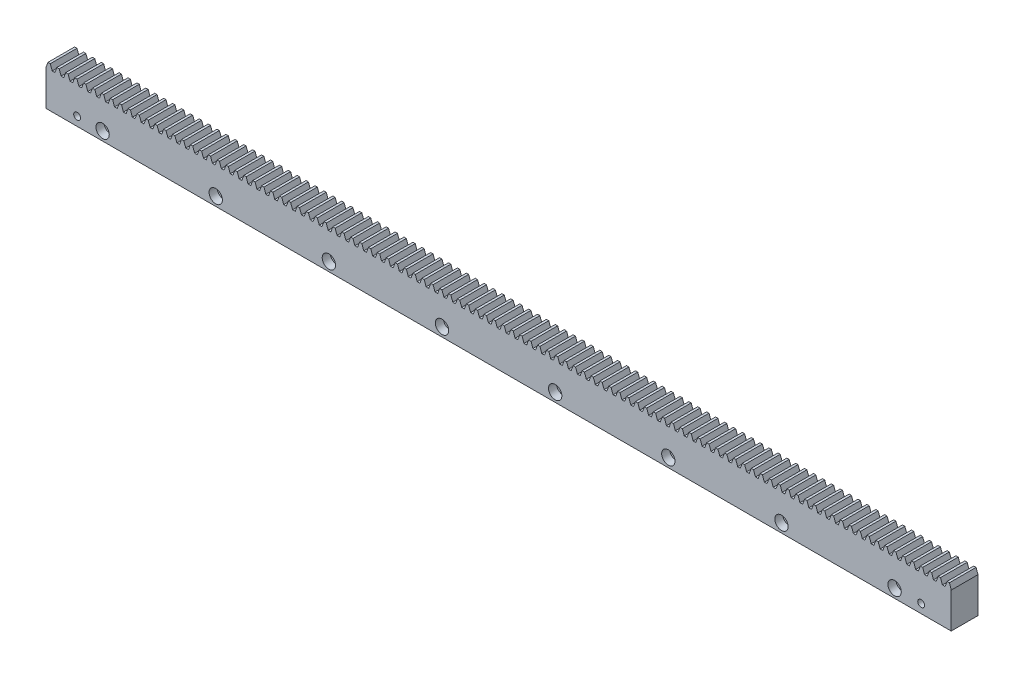
SolidWorks part; units mm, degrees
ref_plane "前视基准面" through (0, 0, 0) normal (0, 0, 1) x (1, 0, 0)
ref_plane "上视基准面" through (0, 0, 0) normal (0, 1, 0) x (1, 0, 0)
ref_plane "右视基准面" through (0, 0, 0) normal (1, 0, 0) x (0, 0, -1)
sketch "草图1" plane through (0, 0, 0) normal (0, 0, 1) x (1, 0, 0)
  line L1 (0, 0) -> (1017.9, 0)
  line L2 (0, 0) -> (0, 40)
  line L3 (0, 40) -> (1017.9, 40)
  line L4 (1017.9, 0) -> (1017.9, 40)
  dimension "D1" = 1017.9
  dimension "D2" = 40
extrude "凸台-拉伸1" add sketch "草图1" along normal blind 30
sketch "草图2" plane through (0, 0, 30) normal (0, 0, 1) x (1, 0, 0)
  line L0 (0, 63.7517) -> (0, -24.099) construction
  line L1 (3.5, 68.5728) -> (3.5, -19.2779) construction
  line L2 (7, 58.1883) -> (7, 38.4338) construction
  line L3 (-2.7333, 46) -> (10.9231, 46) construction
  line L5 (1017.9, 40) -> (0, 40) construction
  line L6 (0, 40) -> (2.1838, 46)
  line L7 (2.1838, 46) -> (4.8162, 46)
  line L8 (4.8162, 46) -> (7, 40)
  line L9 (0, 40) -> (7, 40)
  dimension "D1" = 3.5
  dimension "D2" = 3.5
  dimension "D3" = 6
  dimension "D4" = 20
  dimension "D5" = 20
extrude "凸台-拉伸2" add sketch "草图2" against normal blind 30
pattern_linear "阵列(线性)1" count 102 spacing 10.01 along (1, 0, 0) of "凸台-拉伸2"
sketch "草图3" plane through (0, 0, 30) normal (0, 0, 1) x (1, 0, 0)
  line L0 (-24.859, 10) -> (190.0817, 10) construction
  line L1 (35, 76.1082) -> (35, -38.8584) construction
  line L2 (0, 40) -> (0, 0) construction
  line L3 (0, 0) -> (1017.9, 0) construction
  circle A0 centre (35, 10) radius 3.85
  dimension "D3" = 7.7
  dimension "D1" = 35
  dimension "D2" = 10
extrude "切除-拉伸1" cut sketch "草图3" against normal up to next
pattern_linear "阵列(线性)2" count 2 spacing 949.1 along (1, 0, 0) of "切除-拉伸1"
sketch "草图4" plane through (0, 0, 30) normal (0, 0, 1) x (1, 0, 0)
  line L0 (35, 10) -> (103.7, 10) construction
  line L1 (0, 40) -> (0, 0) construction
  circle A0 centre (63.63, 10) radius 7.5
  dimension "D2" = 15
  dimension "D1" = 63.63
extrude "切除-拉伸2" cut sketch "草图4" against normal blind 9
sketch "草图5" plane through (0, 0, 21) normal (0, 0, 1) x (1, 0, 0)
  circle A0 centre (63.63, 10) radius 5
  dimension "D1" = 10
extrude "切除-拉伸3" cut sketch "草图5" against normal up to next
pattern_linear "阵列(线性)3" count 8 spacing 127.23 along (1, 0, 0) of "切除-拉伸3", "切除-拉伸2"
